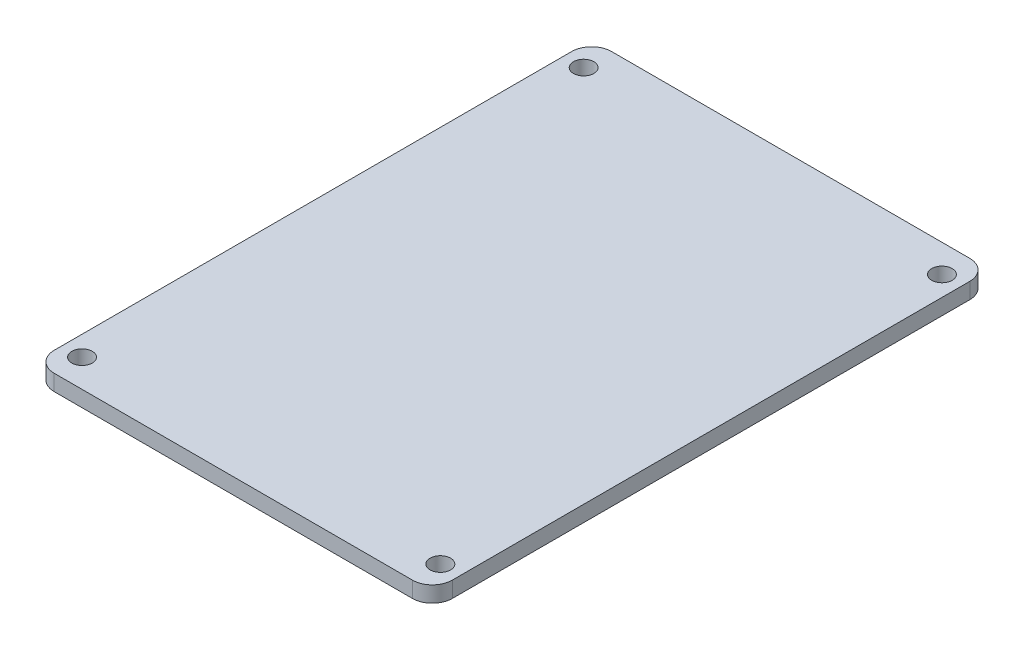
SolidWorks part; units mm, degrees
ref_plane "Front Plane" through (0, 0, 0) normal (0, 0, 1) x (1, 0, 0)
ref_plane "Top Plane" through (0, 0, 0) normal (0, 1, 0) x (1, 0, 0)
ref_plane "Right Plane" through (0, 0, 0) normal (1, 0, 0) x (0, 0, -1)
sketch "Sketch1" plane through (0, 0, 0) normal (0, 1, 0) x (1, 0, 0)
  line L0 (0, 0) -> (31.75, 0) construction
  line L1 (-28.575, 44.45) -> (28.575, 44.45)
  line L2 (-31.75, 41.275) -> (-31.75, -41.275)
  line L3 (-28.575, -44.45) -> (28.575, -44.45)
  line L4 (31.75, 41.275) -> (31.75, -41.275)
  line L5 (-31.75, 44.45) -> (31.75, -44.45) construction
  line L6 (-31.75, -44.45) -> (31.75, 44.45) construction
  line L7 (0, 0) -> (0, 44.45) construction
  circle A1 centre (28.575, 40.005) radius 1.6319
  circle A3 centre (28.575, -40.005) radius 1.6319
  circle A4 centre (-28.575, -40.005) radius 1.6319
  circle A5 centre (-28.575, 40.005) radius 1.6319
  arc A6 (-31.75, -41.275) -> (-28.575, -44.45) centre (-28.575, -41.275) ccw
  arc A7 (28.575, -44.45) -> (31.75, -41.275) centre (28.575, -41.275) ccw
  arc A8 (28.575, 44.45) -> (31.75, 41.275) centre (28.575, 41.275) cw
  arc A9 (-28.575, 44.45) -> (-31.75, 41.275) centre (-28.575, 41.275) ccw
  point P0 (0, 0)
  dimension "D4" = 3.2639
  dimension "D5" = 3.175
  dimension "D1" = 88.9
  dimension "D2" = 63.5
  dimension "D3" = 3.175
extrude "Boss-Extrude1" add sketch "Sketch1" along normal blind 2.54
